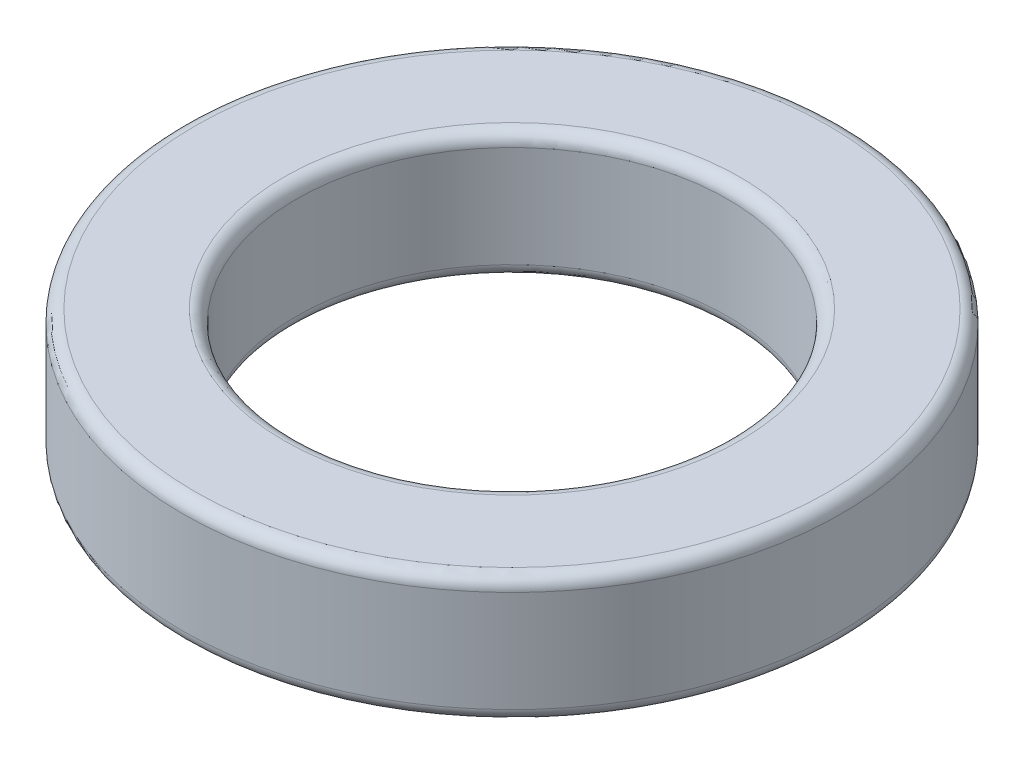
SolidWorks part; units mm, degrees
ref_plane "Спереди" through (0, 0, 0) normal (0, 0, 1) x (1, 0, 0)
ref_plane "Сверху" through (0, 0, 0) normal (0, 1, 0) x (1, 0, 0)
ref_plane "Справа" through (0, 0, 0) normal (1, 0, 0) x (0, 0, -1)
sketch "Эскиз1" plane through (0, 0, 0) normal (0, 1, 0) x (1, 0, 0)
  circle A0 centre (0, 0) radius 8.5
  circle A1 centre (0, 0) radius 13
  dimension "D1" = 17
  dimension "D2" = 26
extrude "Бобышка-Вытянуть1" add sketch "Эскиз1" along normal blind 5
fillet "Скругление1" radius 0.5 4 edges at (0, 0, 8.5) (0, 0, 13) (0, 5, 8.5) (0, 5, 13)
